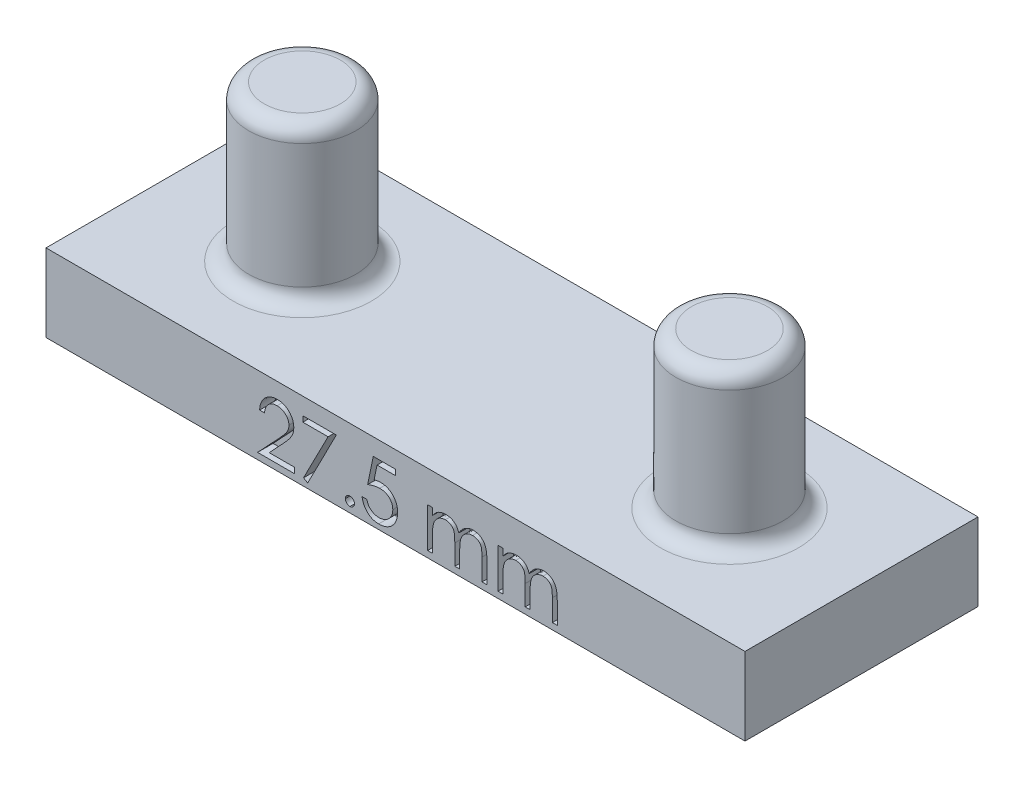
SolidWorks part; units mm, degrees
ref_plane "Front Plane" through (0, 0, 0) normal (0, 0, 1) x (1, 0, 0)
ref_plane "Top Plane" through (0, 0, 0) normal (0, 1, 0) x (1, 0, 0)
ref_plane "Right Plane" through (0, 0, 0) normal (1, 0, 0) x (0, 0, -1)
sketch "Sketch1" plane through (0, 0, 0) normal (0, 1, 0) x (1, 0, 0)
  circle A0 centre (-41.8213, 3.1021) radius 3.4487
  circle A1 centre (-14.3213, 3.1021) radius 3.4487
  dimension "D1" = 27.5
extrude "Boss-Extrude1" add sketch "Sketch1" along normal blind 10
sketch "Sketch2" plane through (0, 0, 0) normal (0, -1, 0) x (1, 0, 0)
  line L1 (-50.8213, 4.3979) -> (-5.8213, 4.3979)
  line L2 (-50.8213, 4.3979) -> (-50.8213, -10.6021)
  line L3 (-50.8213, -10.6021) -> (-5.8213, -10.6021)
  line L4 (-5.8213, 4.3979) -> (-5.8213, -10.6021)
  circle A0 centre (-41.8213, -3.1021) radius 3.4487 construction
  dimension "D1" = 45
  dimension "D2" = 15
  dimension "D3" = 7.5
  dimension "D4" = 9
extrude "Boss-Extrude2" add sketch "Sketch2" along normal blind 5
sketch "Sketch3" plane through (0, 0, 4.3979) normal (0, 0, 1) x (1, 0, 0)
  line L0 (-7.1347, -4.5918) -> (-47.7505, -4.5918) construction
  text T0 "27.5 mm"
extrude "Cut-Extrude1" cut sketch "Sketch3" against normal blind 1
fillet "Fillet1" radius 1 4 edges at (-41.8213, 0, 0.3466) (-14.3213, 0, -6.5508) (-14.3213, 10, 0.3466) (-41.8213, 10, 0.3466)
